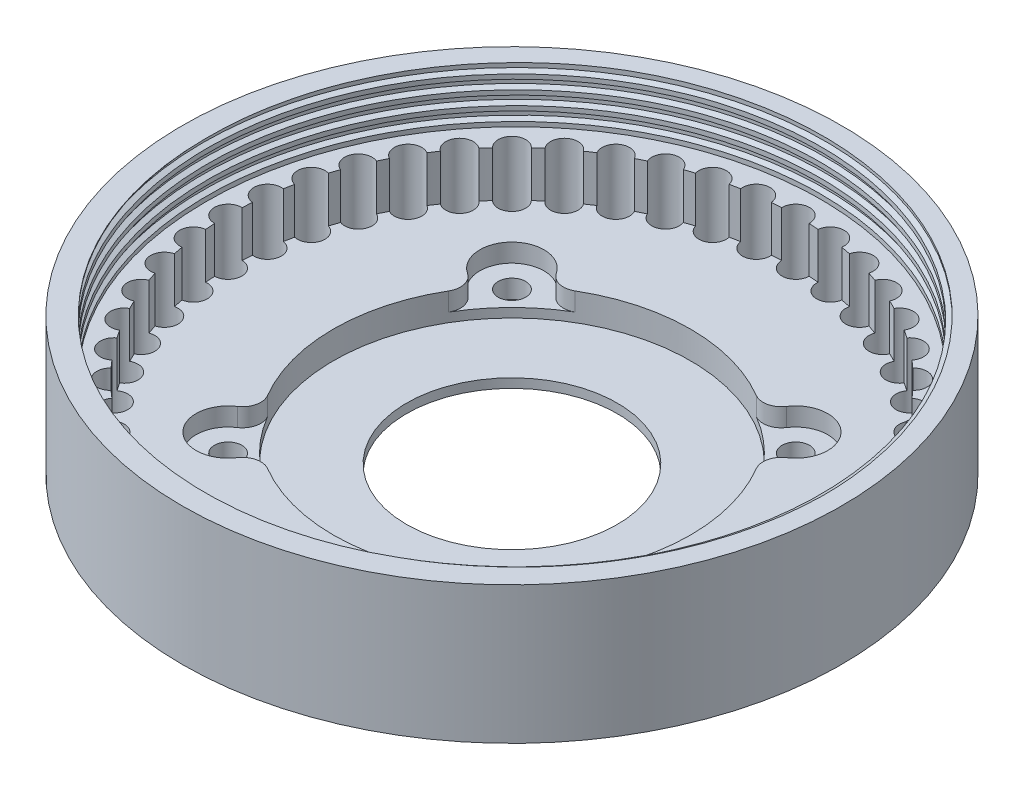
SolidWorks part; units mm, degrees
ref_plane "Front Plane" through (0, 0, 0) normal (0, 0, 1) x (1, 0, 0)
ref_plane "Top Plane" through (0, 0, 0) normal (0, 1, 0) x (1, 0, 0)
ref_plane "Right Plane" through (0, 0, 0) normal (1, 0, 0) x (0, 0, -1)
sketch "Sketch1" plane through (0, 0, 0) normal (0, 1, 0) x (1, 0, 0)
  circle A1 centre (0, 0) radius 36
  dimension "D1" = 72
extrude "Boss-Extrude1" add sketch "Sketch1" along normal blind 15
sketch "Sketch2" plane through (0, 15, 0) normal (0, 1, 0) x (1, 0, 0)
  circle A1 centre (0, 0) radius 33.5
  circle A3 centre (0, 0) radius 36 construction
  dimension "D1" = 2.5
extrude "Cut-Extrude4" cut sketch "Sketch2" against normal blind 6
sketch "Sketch4" plane through (0, 9, 0) normal (0, 1, 0) x (1, 0, 0)
  line L0 (-1027.5714, 36) -> (48972.4286, 36) construction
  circle A0 centre (0, 31) radius 1.5
  circle A2 centre (0, 0) radius 36 construction
  dimension "D1" = 3
  dimension "D2" = 5
extrude "Cut-Extrude5" cut sketch "Sketch4" against normal blind 8
pattern_circular "CirPattern2" count 48 over 360 about axis through (0, 0, 0) along (0, 1, 0) of "Cut-Extrude5"
sketch "Sketch5" plane through (0, 9, 0) normal (0, 1, 0) x (1, 0, 0)
  circle A0 centre (0, 0) radius 31
  dimension "D1" = 62
extrude "Cut-Extrude6" cut sketch "Sketch5" against normal blind 5
sketch "Sketch6" plane through (0, 4, 0) normal (0, 1, 0) x (1, 0, 0)
  circle A0 centre (0, 0) radius 19.5
  dimension "D1" = 39
extrude "Cut-Extrude7" cut sketch "Sketch6" against normal blind 3
sketch "Sketch7" plane through (0, 4, 0) normal (0, 1, 0) x (1, 0, 0)
  line L1 (-15.5, -15.5) -> (15.5, -15.5) construction
  line L2 (-15.5, -15.5) -> (-15.5, 15.5) construction
  line L3 (-15.5, 15.5) -> (15.5, 15.5) construction
  line L4 (15.5, -15.5) -> (15.5, 15.5) construction
  line L5 (-15.5, -15.5) -> (15.5, 15.5) construction
  line L6 (-15.5, 15.5) -> (15.5, -15.5) construction
  circle A0 centre (15.5, 15.5) radius 1.5
  circle A1 centre (15.5, -15.5) radius 1.5
  circle A2 centre (-15.5, 15.5) radius 1.5
  circle A3 centre (-15.5, -15.5) radius 1.5
  point P0 (0, 0)
  dimension "D2" = 3
  dimension "D1" = 31
extrude "Cut-Extrude8" cut sketch "Sketch7" against normal through all
sketch "Sketch9" plane through (0, 4, 0) normal (0, 1, 0) x (1, 0, 0)
  circle A0 centre (15.5, 15.5) radius 3.5
  circle A1 centre (-15.5, 15.5) radius 3.5
  circle A2 centre (-15.5, -15.5) radius 3.5
  circle A3 centre (15.5, -15.5) radius 3.5
  dimension "D1" = 7
extrude "Cut-Extrude9" cut sketch "Sketch9" against normal blind 2
fillet "Fillet1" radius 2 8 edges at (15.3685, 3, 12.0025) (12.0025, 3, 15.3685) (15.3685, 3, -12.0025) (12.0025, 3, -15.3685) (-15.3685, 3, 12.0025) (-12.0025, 3, 15.3685) (-12.0025, 3, -15.3685) (-15.3685, 3, -12.0025)
sketch "Sketch10" plane through (0, 1, 0) normal (0, 1, 0) x (1, 0, 0)
  circle A0 centre (0, 0) radius 11.5
  dimension "D1" = 23
extrude "Cut-Extrude10" cut sketch "Sketch10" against normal through all
sketch "Sketch13" plane through (0, 9, 0) normal (0, 1, 0) x (1, 0, 0)
  circle A0 centre (0, 0) radius 33.5
  circle A1 centre (0, 0) radius 33.5 construction
curve "Helix/Spiral1" pitch 1.5 height 7.5 turns 5
sketch "Sketch14" plane through (0, 0, 0) normal (0, 0, 1) x (1, 0, 0)
  line L1 (-33.5, 16.5) -> (-33.5, 15.5)
  line L2 (-33.5, 15.5) -> (-34, 15.75)
  line L3 (-34, 15.75) -> (-34, 16.25)
  line L4 (-34, 16.25) -> (-33.5, 16.5)
  line L5 (-1033.5, 16) -> (48966.5, 16) construction
  spline S4 degree 3 poles (-33.5, 9) (-33.5, 9.0195) (-32.8239, 9.0586) (-29.8425, 9.1172) (-25.0723, 9.1758) (-18.7994, 9.2344) (-11.3997, 9.293) (-3.3167, 9.3516) (4.9651, 9.4102) (12.9493, 9.4687) (20.1573, 9.5273) (26.1571, 9.5859) (30.5892, 9.6445) (33.1878, 9.7031) (33.7973, 9.7617) (32.381, 9.8203) (29.0238, 9.8789) (23.9271, 9.9375) (17.3962, 9.9961) (9.8227, 10.0547) (1.6604, 10.1133) (-6.6015, 10.1719) (-14.4676, 10.2305) (-21.4666, 10.2891) (-27.179, 10.3477) (-31.2623, 10.4062) (-33.4718, 10.4648) (-33.6751, 10.5234) (-31.86, 10.582) (-28.1353, 10.6406) (-22.7242, 10.6992) (-15.9511, 10.7578) (-5.6456, 10.8359) (5.6456, 10.9141) (15.9511, 10.9922) (22.7242, 11.0508) (28.1353, 11.1094) (31.86, 11.168) (33.6751, 11.2266) (33.4718, 11.2852) (31.2623, 11.3438) (27.179, 11.4023) (21.4666, 11.4609) (14.4676, 11.5195) (6.6015, 11.5781) (-1.6604, 11.6367) (-9.8227, 11.6953) (-17.3962, 11.7539) (-23.9271, 11.8125) (-29.0238, 11.8711) (-32.381, 11.9297) (-33.7973, 11.9883) (-33.1878, 12.0469) (-30.5892, 12.1055) (-26.1571, 12.1641) (-20.1573, 12.2227) (-12.9493, 12.2813) (-4.9651, 12.3398) (3.3167, 12.3984) (11.3997, 12.457) (18.7994, 12.5156) (25.0723, 12.5742) (29.8425, 12.6328) (32.8239, 12.6914) (33.838, 12.75) (32.8239, 12.8086) (29.8425, 12.8672) (25.0723, 12.9258) (18.7994, 12.9844) (11.3997, 13.043) (3.3167, 13.1016) (-4.9651, 13.1602) (-12.9493, 13.2188) (-20.1573, 13.2773) (-26.1571, 13.3359) (-30.5892, 13.3945) (-33.1878, 13.4531) (-33.7973, 13.5117) (-32.381, 13.5703) (-29.0238, 13.6289) (-23.9271, 13.6875) (-17.3962, 13.7461) (-9.8227, 13.8047) (-1.6604, 13.8633) (6.6015, 13.9219) (14.4676, 13.9805) (21.4666, 14.0391) (27.179, 14.0977) (31.2623, 14.1562) (33.4718, 14.2148) (33.6751, 14.2734) (31.86, 14.332) (28.1353, 14.3906) (22.7242, 14.4492) (15.9511, 14.5078) (5.6456, 14.5859) (-5.6456, 14.6641) (-15.9511, 14.7422) (-22.7242, 14.8008) (-28.1353, 14.8594) (-31.86, 14.918) (-33.6751, 14.9766) (-33.4718, 15.0352) (-31.2623, 15.0937) (-27.179, 15.1523) (-21.4666, 15.2109) (-14.4676, 15.2695) (-6.6015, 15.3281) (1.6604, 15.3867) (9.8227, 15.4453) (17.3962, 15.5039) (23.9271, 15.5625) (29.0238, 15.6211) (32.381, 15.6797) (33.7973, 15.7383) (33.1878, 15.7969) (30.5892, 15.8555) (26.1571, 15.9141) (20.1573, 15.9727) (12.9493, 16.0313) (4.9651, 16.0898) (-3.3167, 16.1484) (-11.3997, 16.207) (-18.7994, 16.2656) (-25.0723, 16.3242) (-29.8425, 16.3828) (-32.8239, 16.4414) (-33.5, 16.4805) (-33.5, 16.5) knots 0 0 0 0 0.007812 0.015625 0.023437 0.03125 0.039062 0.046875 0.054687 0.0625 0.070312 0.078125 0.085937 0.09375 0.101562 0.109375 0.117187 0.125 0.132812 0.140625 0.148437 0.15625 0.164062 0.171875 0.179687 0.1875 0.195312 0.203125 0.210937 0.21875 0.226562 0.234375 0.242187 0.257812 0.265625 0.273437 0.28125 0.289062 0.296875 0.304687 0.3125 0.320312 0.328125 0.335937 0.34375 0.351562 0.359375 0.367187 0.375 0.382812 0.390625 0.398437 0.40625 0.414062 0.421875 0.429687 0.4375 0.445312 0.453125 0.460937 0.46875 0.476562 0.484375 0.492187 0.5 0.507812 0.515625 0.523437 0.53125 0.539062 0.546875 0.554687 0.5625 0.570312 0.578125 0.585937 0.59375 0.601562 0.609375 0.617187 0.625 0.632812 0.640625 0.648437 0.65625 0.664062 0.671875 0.679687 0.6875 0.695312 0.703125 0.710937 0.71875 0.726562 0.734375 0.742187 0.757812 0.765625 0.773437 0.78125 0.789062 0.796875 0.804687 0.8125 0.820312 0.828125 0.835937 0.84375 0.851562 0.859375 0.867187 0.875 0.882812 0.890625 0.898437 0.90625 0.914062 0.921875 0.929688 0.9375 0.945312 0.953125 0.960937 0.96875 0.976562 0.984375 0.992188 1 1 1 1 construction
  point P9 (-33.5, 16)
  dimension "D1" = 0.5
  dimension "D2" = 1
  dimension "D3" = 0.5
sweep "Cut-Sweep5" cut profiles "Sketch14" path "Helix/Spiral1" align with end faces yes
